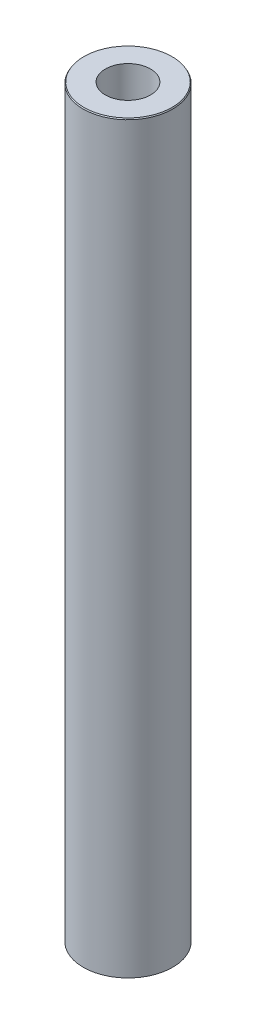
SolidWorks part; units mm, degrees
ref_plane "Front Plane" through (0, 0, 0) normal (0, 0, 1) x (1, 0, 0)
ref_plane "Top Plane" through (0, 0, 0) normal (0, 1, 0) x (1, 0, 0)
ref_plane "Right Plane" through (0, 0, 0) normal (1, 0, 0) x (0, 0, -1)
sketch "Sketch1" plane through (0, 0, 0) normal (0, 1, 0) x (1, 0, 0)
  circle A0 centre (0, 0) radius 12.5
  dimension "SHAFT_OD" = 25
extrude "Boss-Extrude1" add sketch "Sketch1" along normal blind 208.2687
sketch "Sketch2" plane through (0, 0, 0) normal (0, 1, 0) x (1, 0, 0)
  circle A0 centre (0, 0) radius 6.3094
  dimension "BORE_D" = 12.6189
extrude "Cut-Extrude1" cut sketch "Sketch2" along normal through all
chamfer "Chamfer1" distance 0.3184 angle 30 2 edges at (0, 208.2687, 12.5) (0, 0, 12.5) first distance on face at (0, 208.2687, 12.5) first distance on face at (0, 0, 6.3094)
